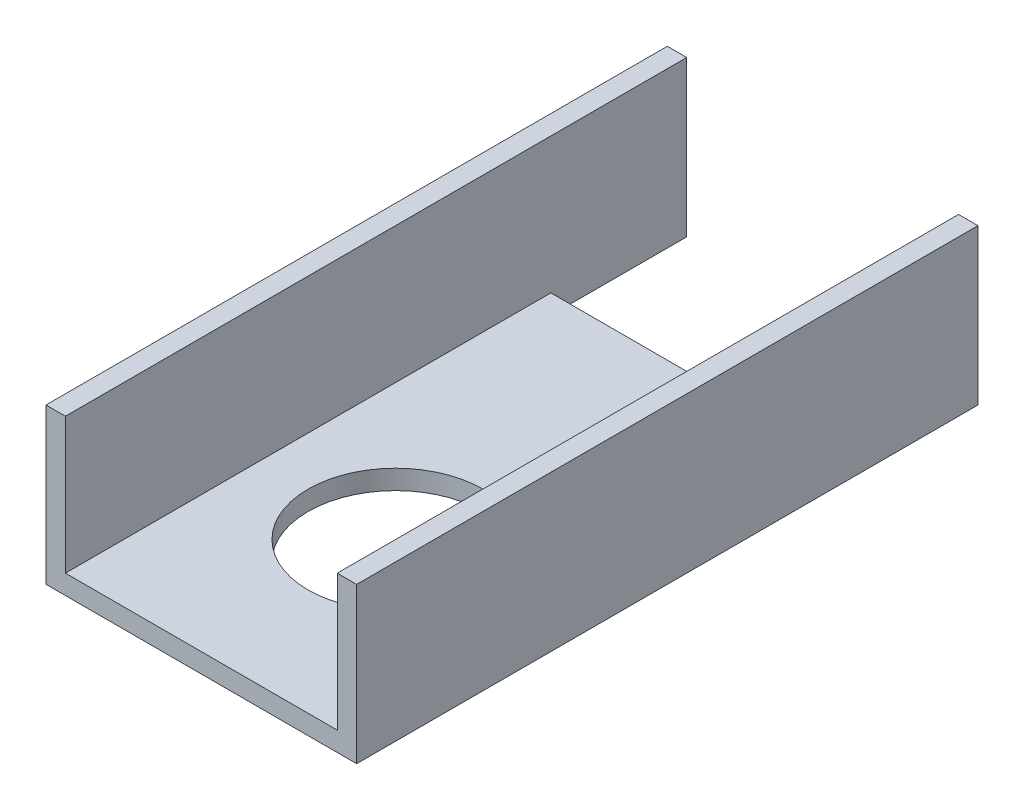
SolidWorks part; units mm, degrees
material "6063-T6"
ref_plane "Front" through (0, 0, 0) normal (0, 0, 1) x (1, 0, 0)
ref_plane "Top" through (0, 0, 0) normal (0, 1, 0) x (1, 0, 0)
ref_plane "Right" through (0, 0, 0) normal (1, 0, 0) x (0, 0, -1)
sketch "Sketch1" plane through (0, 0, 0) normal (0, 0, 1) x (1, 0, 0)
  line L0 (47.625, 3.175) -> (47.625, 25.4)
  line L1 (0, 0) -> (50.8, 0)
  line L2 (0, 0) -> (0, 25.4)
  line L4 (50.8, 0) -> (50.8, 25.4)
  line L5 (3.175, 3.175) -> (47.625, 3.175)
  line L6 (3.175, 3.175) -> (3.175, 25.4)
  line L7 (50.8, 25.4) -> (47.625, 25.4)
  line L8 (0, 25.4) -> (3.175, 25.4)
  dimension "D1" = 25.4
  dimension "D2" = 50.8
  dimension "D3" = 3.175
extrude "Boss-Extrude1" add sketch "Sketch1" along normal blind 101.6
sketch "Sketch2" plane through (0, 0, 0) normal (0, -1, 0) x (1, 0, 0)
  line L0 (25.4, 69.85) -> (25.4, 101.6) construction
  line L1 (0, 101.6) -> (50.8, 101.6) construction
  circle A0 centre (25.4, 69.85) radius 14.2875
  dimension "D1" = 28.575
  dimension "D2" = 31.75
extrude "Cut-Extrude1" cut sketch "Sketch2" against normal up to next
sketch "Sketch3" plane through (0, 3.175, 0) normal (0, 1, 0) x (1, 0, 0)
  line L0 (3.175, -101.6) -> (3.175, 0) construction
  line L1 (3.175, -22.225) -> (47.625, -22.225)
  line L2 (3.175, -22.225) -> (3.175, 0)
  line L3 (3.175, 0) -> (47.625, 0)
  line L4 (47.625, -22.225) -> (47.625, 0)
  line L5 (3.175, -22.225) -> (47.625, 0) construction
  line L6 (3.175, 0) -> (47.625, -22.225) construction
  point P4 (25.4, -11.1125)
  dimension "D1" = 22.225
extrude "Cut-Extrude2" cut sketch "Sketch3" against normal up to next
